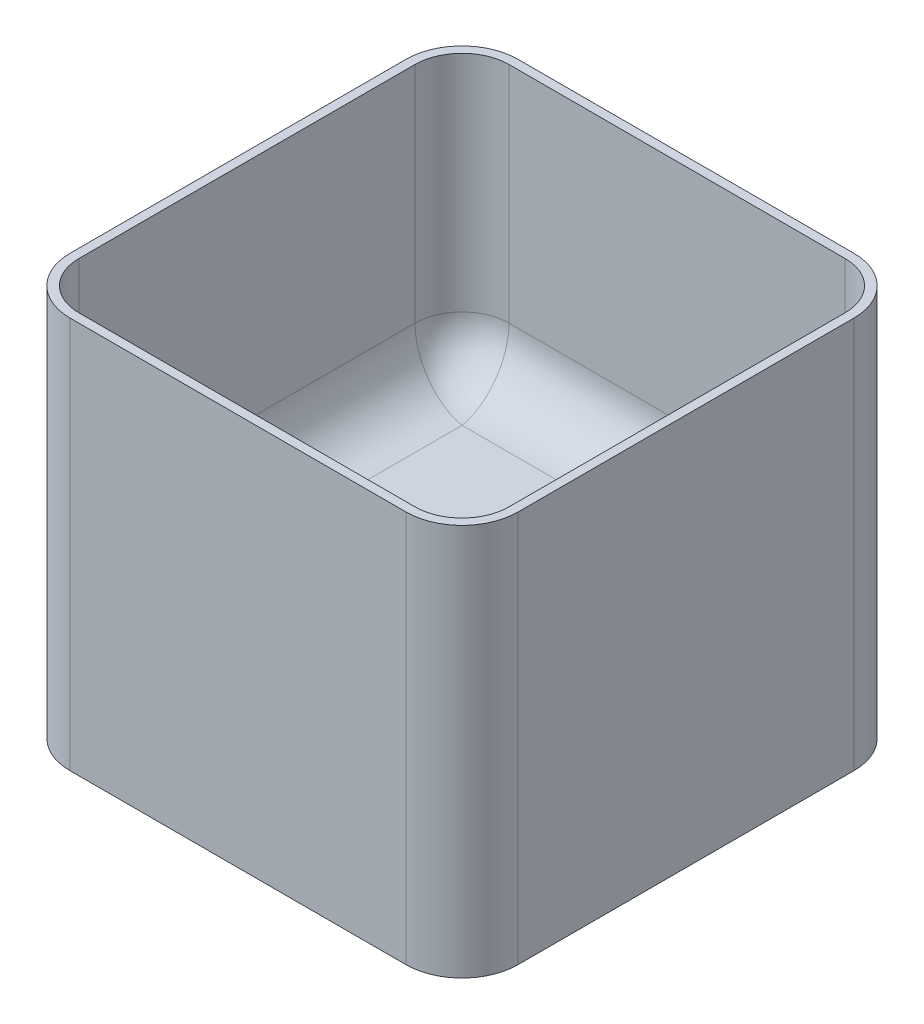
SolidWorks part; units mm, degrees
ref_plane "Спереди" through (0, 0, 0) normal (0, 0, 1) x (1, 0, 0)
ref_plane "Сверху" through (0, 0, 0) normal (0, 1, 0) x (1, 0, 0)
ref_plane "Справа" through (0, 0, 0) normal (1, 0, 0) x (0, 0, -1)
sketch "Sketch1" plane through (0, 0, 0) normal (0, 1, 0) x (1, 0, 0)
  line L1 (-40, -40) -> (40, -40)
  line L2 (-40, -40) -> (-40, 40)
  line L3 (-40, 40) -> (40, 40)
  line L4 (40, -40) -> (40, 40)
  line L5 (-40, -40) -> (40, 40) construction
  line L6 (-40, 40) -> (40, -40) construction
  point P0 (0, 0)
extrude "Boss-Extrude1" add sketch "Sketch1" along normal blind 70
sketch "Sketch2" plane through (0, 0, 0) normal (0, -1, 0) x (1, 0, 0)
  circle A0 centre (0, 0) radius 25
  dimension "D1" = 50
extrude "Cut-Extrude1" cut sketch "Sketch2" against normal blind 10
sketch "Sketch3" plane through (0, 10, 0) normal (0, -1, 0) x (1, 0, 0)
  circle A0 centre (0, 0) radius 17.35
extrude "Cut-Extrude2" cut sketch "Sketch3" against normal up to next
fillet "Fillet2" radius 10 4 edges at (-40, 35, 40) (40, 35, 40) (40, 35, -40) (-40, 35, -40)
fillet "Fillet3" radius 10 1 edges at (0, 10, -25)
sketch3d "3DSketch3"
  line L0 (-30, 70, 38.4) -> (30, 70, 38.4)
  line L1 (38.4, 70, 30) -> (38.4, 70, -30)
  line L2 (30, 70, -38.4) -> (-30, 70, -38.4)
  line L3 (-38.4, 70, -30) -> (-38.4, 70, 30)
  line L4 (-30, 70, 38.4) -> (30, 70, 38.4)
  line L5 (38.4, 70, 30) -> (38.4, 70, -30)
  line L6 (30, 70, -38.4) -> (-30, 70, -38.4)
  line L7 (-38.4, 70, -30) -> (-38.4, 70, 30)
  arc A0 (30, 70, 38.4) -> (38.4, 70, 30) centre (30, 70, 30) ccw
  arc A1 (38.4, 70, -30) -> (30, 70, -38.4) centre (30, 70, -30) ccw
  arc A2 (-30, 70, -38.4) -> (-38.4, 70, -30) centre (-30, 70, -30) ccw
  arc A3 (-38.4, 70, 30) -> (-30, 70, 38.4) centre (-30, 70, 30) ccw
  arc A4 (30, 70, 38.4) -> (38.4, 70, 30) centre (30, 70, 30) ccw
  arc A5 (38.4, 70, -30) -> (30, 70, -38.4) centre (30, 70, -30) ccw
  arc A6 (-30, 70, -38.4) -> (-38.4, 70, -30) centre (-30, 70, -30) ccw
  arc A7 (-38.4, 70, 30) -> (-30, 70, 38.4) centre (-30, 70, 30) ccw
  point P4 (30, 78.4, 30)
  point P8 (30, 78.4, -30)
  point P12 (-30, 78.4, -30)
  point P15 (-30, 78.4, 30)
  point P16 (30, 78.4, 30)
  point P17 (30, 78.4, -30)
  point P18 (-30, 78.4, -30)
  point P19 (-30, 78.4, 30)
  dimension "D1" = 1.6
extrude "Cut-Extrude5" cut sketch "3DSketch3" along direction (0, -1, 0) on the side against the normal blind 50
fillet "Fillet6" radius 10 8 edges
